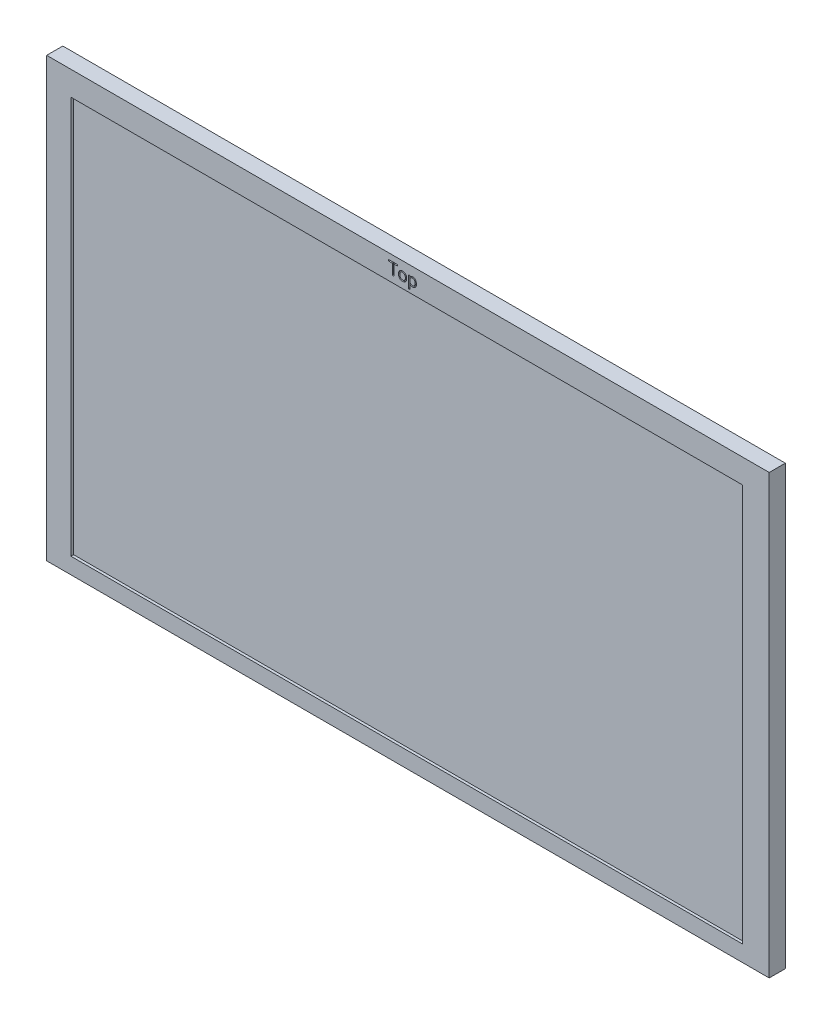
SolidWorks part; units mm, degrees
material "AISI 1020"
ref_plane "Front" through (0, 0, 0) normal (0, 0, 1) x (1, 0, 0)
ref_plane "Top" through (0, 0, 0) normal (0, 1, 0) x (1, 0, 0)
ref_plane "Right" through (0, 0, 0) normal (1, 0, 0) x (0, 0, -1)
ref_axis "X Axis" through (-80.9, 0, 0) along (1, 0, 0)
ref_axis "Y Axis" through (0, -50, 0) along (0, 1, 0)
ref_axis "Z Axis" through (0, 0, -80.9) along (0, 0, 1)
sketch "Sketch2" plane through (0, 0, 0) normal (0, 0, 1) x (1, 0, 0)
  line L1 (-106.7594, -64.6906) -> (106.7594, -64.6906)
  line L2 (-106.7594, -64.6906) -> (-106.7594, 64.6906)
  line L3 (-106.7594, 64.6906) -> (106.7594, 64.6906)
  line L4 (106.7594, -64.6906) -> (106.7594, 64.6906)
  line L5 (-106.7594, -64.6906) -> (106.7594, 64.6906) construction
  line L6 (-106.7594, 64.6906) -> (106.7594, -64.6906) construction
  point P0 (0, 0)
  dimension "D1" = 129.3812
  dimension "D2" = 213.5188
extrude "Boss-Extrude1" add sketch "Sketch2" along normal blind 4.7625
sketch "Sketch3" plane through (0, 0, 4.7625) normal (0, 0, 1) x (1, 0, 0)
  line L0 (-106.7594, 64.6906) -> (-106.7594, -64.6906) construction
  line L1 (-99.6156, 57.5532) -> (98.8219, 57.5532)
  line L2 (-99.6156, 57.5532) -> (-99.6156, -59.9281)
  line L3 (-99.6156, -59.9281) -> (98.8219, -59.9281)
  line L4 (98.8219, 57.5532) -> (98.8219, -59.9281)
  line L5 (106.7594, -64.6906) -> (106.7594, 64.6906) construction
  line L6 (106.7594, 64.6906) -> (-106.7594, 64.6906) construction
  line L7 (-106.7594, -64.6906) -> (106.7594, -64.6906) construction
  dimension "D1" = 7.1437
  dimension "D2" = 7.9375
  dimension "D3" = 7.1374
  dimension "D4" = 4.7625
extrude "Cut-Extrude1" cut sketch "Sketch3" against normal blind 0.7937
sketch "Sketch4" plane through (0, 0, 4.7625) normal (0, 0, 1) x (1, 0, 0)
  line L0 (-5.754, 59.4699) -> (6.3503, 59.4699) construction
  text T0 "Top"
extrude "Cut-Extrude3" cut sketch "Sketch4" against normal blind 0.3969
sketch "Sketch5" plane through (0, 0, 4.7625) normal (0, 0, 1) x (1, 0, 0)
  line L0 (0, 0) -> (0, 96.4039) construction
  line L1 (-115.8875, 82.9532) -> (115.8875, 82.9532)
  line L2 (-115.8875, 82.9532) -> (-115.8875, -88.4968)
  line L3 (-115.8875, -88.4968) -> (115.8875, -88.4968)
  line L4 (115.8875, 82.9532) -> (115.8875, -88.4968)
  line L5 (98.8219, 57.5532) -> (-99.6156, 57.5532) construction
  line L6 (-106.7594, -64.6906) -> (106.7594, -64.6906) construction
  dimension "D1" = 231.775
  dimension "D2" = 25.4
  dimension "D3" = 171.45
  dimension "D4" = 23.8061
